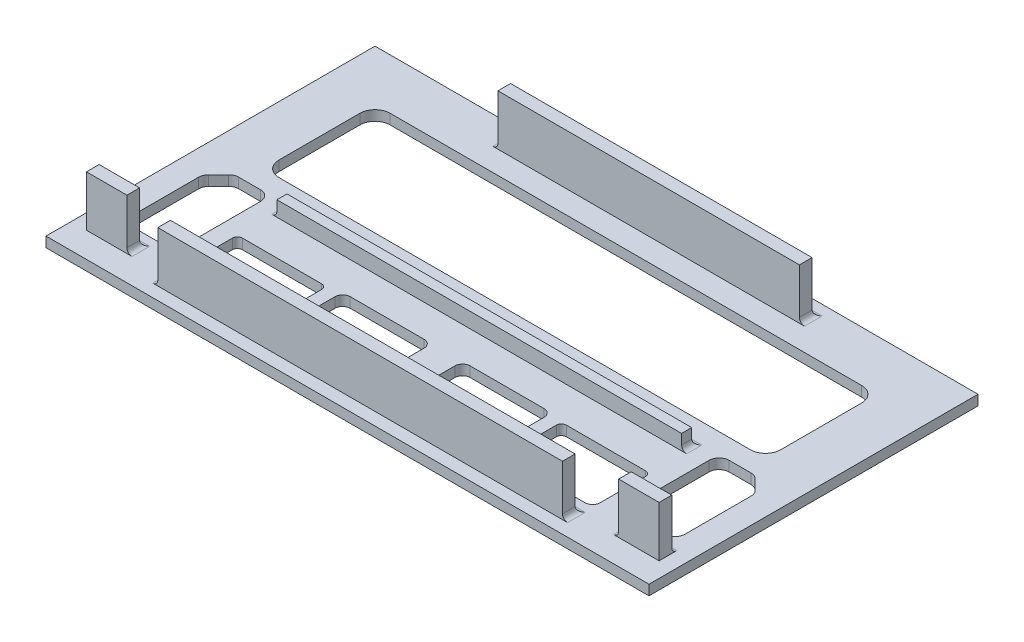
SolidWorks part; units mm, degrees
ref_plane "Front Plane" through (0, 0, 0) normal (0, 0, 1) x (1, 0, 0)
ref_plane "Top Plane" through (0, 0, 0) normal (0, 1, 0) x (1, 0, 0)
ref_plane "Right Plane" through (0, 0, 0) normal (1, 0, 0) x (0, 0, -1)
sketch "Sketch1" plane through (0, 0, 0) normal (0, 1, 0) x (1, 0, 0)
  line L1 (-59.6, -32.52) -> (59.6, -32.52)
  line L2 (-59.6, -32.52) -> (-59.6, 32.52)
  line L3 (-59.6, 32.52) -> (59.6, 32.52)
  line L4 (59.6, -32.52) -> (59.6, 32.52)
  line L5 (-59.6, -32.52) -> (59.6, 32.52) construction
  line L6 (-59.6, 32.52) -> (59.6, -32.52) construction
  point P0 (0, 0)
  dimension "D1" = 119.2
  dimension "D2" = 65.04
extrude "Boss-Extrude1" add sketch "Sketch1" along normal blind 2
ref_plane "Plane1" through (0, 0, 0) normal (-1, 0, 0) x (0, 0, 1)
sketch "Sketch2" plane through (0, 2, 0) normal (0, 1, 0) x (1, 0, 0)
  line L0 (-29.8, 29.52) -> (29.8, 29.52)
  line L1 (59.6, 32.52) -> (-59.6, 32.52) construction
  line L2 (59.6, -32.52) -> (59.6, 32.52) construction
  line L3 (59.6, -27.02) -> (59.6, -29.52)
  line L4 (29.8, 27.02) -> (-29.8, 27.02)
  line L5 (40, -4.48) -> (-40, -4.48)
  line L7 (-29.8, 29.52) -> (-29.8, 27.02)
  line L8 (29.8, 29.52) -> (29.8, 27.02)
  line L9 (-40, -4.48) -> (-40, -6.48)
  line L10 (-40, -6.48) -> (40, -6.48)
  line L11 (40, -6.48) -> (40, -4.48)
  dimension "D1" = 3
  dimension "D2" = 2.5
  dimension "D3" = 39
  dimension "D4" = 29.8
  dimension "D5" = 2
  dimension "D9" = 80
extrude "Boss-Extrude2" add sketch "Sketch2" along normal blind 10 contours L10 L11 L5 L9 | L8 L0 L7 L4 region at (0, 2, -28.27) region at (0, 2, 5.48)
fillet "Fillet1" radius 1 6 edges at (-29.8, 2, -28.27) (29.8, 2, -28.27) (0, 2, -29.52) (-40, 2, 5.48) (40, 2, 5.48) (0, 2, 4.48)
sketch "Sketch3" plane through (0, 12, 0) normal (0, 1, 0) x (1, 0, 0)
  line L0 (-40, -6.48) -> (40, -6.48) construction
  line L1 (40, -6.48) -> (40, -4.48) construction
  line L2 (40, -4.48) -> (-40, -4.48) construction
  line L3 (-40, -4.48) -> (-40, -6.48) construction
  line L4 (40, -8.48) -> (-40, -8.48) construction
  line L5 (-40, -8.48) -> (-40, -10.48) construction
  line L6 (-40, -10.48) -> (40, -10.48) construction
  line L7 (40, -10.48) -> (40, -8.48) construction
  line L8 (-40, -6.48) -> (40, -6.48)
  line L9 (40, -6.48) -> (40, -4.48)
  line L10 (40, -4.48) -> (-40, -4.48)
  line L11 (-40, -4.48) -> (-40, -6.48)
  line L12 (40, -8.48) -> (-40, -8.48)
  line L13 (-40, -8.48) -> (-40, -10.48)
  line L14 (-40, -10.48) -> (40, -10.48)
  line L15 (40, -10.48) -> (40, -8.48)
extrude "Cut-Extrude1" cut sketch "Sketch3" against normal blind 7
sketch "Sketch4" plane through (0, 2, 0) normal (0, 1, 0) x (1, 0, 0)
  line L0 (40, -30.02) -> (-40, -30.02)
  line L1 (-40, -30.02) -> (-40, -27.52)
  line L2 (-40, -27.52) -> (40, -27.52)
  line L3 (40, -27.52) -> (40, -30.02)
  line L4 (-59.6, -32.52) -> (59.6, -32.52) construction
  line L5 (0, 1.1) -> (0, -1.1) construction
  line L6 (48.6, -27.52) -> (56.6, -27.52)
  line L7 (56.6, -27.52) -> (56.6, -25.02)
  line L8 (56.6, -25.02) -> (48.6, -25.02)
  line L9 (48.6, -25.02) -> (48.6, -27.52)
  line L15 (59.6, -32.52) -> (59.6, 32.52) construction
  point P6 (0, -27.52)
  point P15 (52.6, -27.52)
  dimension "D1" = 2.5
  dimension "D2" = 2.5
  dimension "D3" = 80
  dimension "D4" = 2.5
  dimension "D6" = 3
  dimension "D7" = 8
extrude "Boss-Extrude3" add sketch "Sketch4" along normal blind 10
fillet "Fillet2" radius 1 5 edges at (-40, 2, 28.77) (48.6, 2, 26.27) (52.6, 2, 25.02) (40, 2, 28.77) (0, 2, 27.52)
mirror "Mirror1" about plane through (0, 0, 0) normal (-1, 0, 0) of "Boss-Extrude3"
fillet "Fillet3" radius 1 2 edges at (-52.6, 2, 25.02) (-48.6, 2, 26.27)
sketch "Sketch5" plane through (0, 2, 0) normal (0, 1, 0) x (1, 0, 0)
  line L0 (46.6, 22.52) -> (6.3115, 22.52)
  line L1 (6.3115, 22.52) -> (-46.6, 22.52)
  line L2 (-49.6, 19.52) -> (-49.6, 3.52)
  line L3 (-46.6, 0.52) -> (46.6, 0.52)
  line L4 (49.6, 3.52) -> (49.6, 19.52)
  line L5 (59.6, 32.52) -> (-59.6, 32.52) construction
  line L6 (59.6, -32.52) -> (59.6, 32.52) construction
  line L7 (-59.6, 32.52) -> (-59.6, -32.52) construction
  arc A0 (-49.6, 3.52) -> (-46.6, 0.52) centre (-46.6, 3.52) ccw
  arc A1 (-46.6, 22.52) -> (-49.6, 19.52) centre (-46.6, 19.52) ccw
  arc A2 (46.6, 22.52) -> (49.6, 19.52) centre (46.6, 19.52) cw
  arc A3 (46.6, 0.52) -> (49.6, 3.52) centre (46.6, 3.52) ccw
  dimension "D5" = 3
  dimension "D1" = 10
  dimension "D2" = 10
  dimension "D3" = 10
  dimension "D4" = 22
extrude "Cut-Extrude2" cut sketch "Sketch5" against normal blind 10
sketch "Sketch6" plane through (0, 2, 0) normal (0, 1, 0) x (1, 0, 0)
  line L3 (54.0142, -5.9408) -> (52.0453, -3.9719)
  line L4 (50.6311, -3.3862) -> (46.3278, -3.3862)
  line L5 (54.6, -7.3551) -> (54.6, -20.3979)
  line L6 (52.6, -22.3979) -> (46.3278, -22.3979)
  line L7 (44.3278, -20.3979) -> (44.3278, -5.3862)
  line L10 (39.8278, -13.4493) -> (24.2108, -13.4493)
  line L16 (4.044, -24.8936) -> (19.6609, -24.8936)
  line L17 (40.8278, -14.4493) -> (40.8278, -23.3936)
  line L18 (39.3278, -24.8936) -> (24.7108, -24.8936)
  line L19 (23.2108, -23.3936) -> (23.2108, -14.4493)
  line L21 (20.6609, -23.8936) -> (20.6609, -14.3214)
  line L22 (19.1609, -12.8214) -> (4.544, -12.8214)
  line L23 (3.044, -14.3214) -> (3.044, -23.8936)
  line L25 (59.6, -32.52) -> (59.6, 32.52) construction
  line L26 (0, -47.4967) -> (0, 52.968) construction
  line L29 (-4.044, -24.8936) -> (-19.6609, -24.8936)
  line L31 (-3.044, -14.3214) -> (-3.044, -23.8936)
  line L33 (-19.1609, -12.8214) -> (-4.544, -12.8214)
  line L34 (-20.6609, -23.8936) -> (-20.6609, -14.3214)
  line L37 (-39.3278, -24.8936) -> (-24.7108, -24.8936)
  line L39 (-39.8278, -13.4493) -> (-24.2108, -13.4493)
  line L40 (-23.2108, -14.4493) -> (-23.2108, -23.3936)
  line L42 (-40.8278, -23.3936) -> (-40.8278, -14.4493)
  line L43 (-44.3278, -5.3862) -> (-44.3278, -20.3979)
  line L44 (-50.6311, -3.3862) -> (-46.3278, -3.3862)
  line L45 (-54.0142, -5.9408) -> (-52.0453, -3.9719)
  line L46 (-54.6, -20.3979) -> (-54.6, -7.3551)
  line L51 (-52.6, -22.3979) -> (-46.3278, -22.3979)
  arc A1 (44.3278, -5.3862) -> (46.3278, -3.3862) centre (46.3278, -5.3862) cw
  arc A2 (52.0453, -3.9719) -> (50.6311, -3.3862) centre (50.6311, -5.3862) ccw
  arc A3 (54.6, -7.3551) -> (54.0142, -5.9408) centre (52.6, -7.3551) ccw
  arc A5 (46.3278, -22.3979) -> (44.3278, -20.3979) centre (46.3278, -20.3979) cw
  arc A8 (54.6, -20.3979) -> (52.6, -22.3979) centre (52.6, -20.3979) cw
  arc A10 (4.544, -12.8214) -> (3.044, -14.3214) centre (4.544, -14.3214) ccw
  arc A11 (20.6609, -14.3214) -> (19.1609, -12.8214) centre (19.1609, -14.3214) ccw
  arc A15 (24.7108, -24.8936) -> (23.2108, -23.3936) centre (24.7108, -23.3936) cw
  arc A16 (40.8278, -23.3936) -> (39.3278, -24.8936) centre (39.3278, -23.3936) cw
  arc A18 (3.044, -23.8936) -> (4.044, -24.8936) centre (4.044, -23.8936) ccw
  arc A19 (20.6609, -23.8936) -> (19.6609, -24.8936) centre (19.6609, -23.8936) cw
  arc A21 (40.8278, -14.4493) -> (39.8278, -13.4493) centre (39.8278, -14.4493) ccw
  arc A23 (24.2108, -13.4493) -> (23.2108, -14.4493) centre (24.2108, -14.4493) ccw
  arc A26 (-3.044, -23.8936) -> (-4.044, -24.8936) centre (-4.044, -23.8936) cw
  arc A27 (-20.6609, -23.8936) -> (-19.6609, -24.8936) centre (-19.6609, -23.8936) ccw
  arc A29 (-4.544, -12.8214) -> (-3.044, -14.3214) centre (-4.544, -14.3214) cw
  arc A31 (-20.6609, -14.3214) -> (-19.1609, -12.8214) centre (-19.1609, -14.3214) cw
  arc A35 (-40.8278, -23.3936) -> (-39.3278, -24.8936) centre (-39.3278, -23.3936) ccw
  arc A36 (-24.7108, -24.8936) -> (-23.2108, -23.3936) centre (-24.7108, -23.3936) ccw
  arc A37 (-24.2108, -13.4493) -> (-23.2108, -14.4493) centre (-24.2108, -14.4493) cw
  arc A40 (-40.8278, -14.4493) -> (-39.8278, -13.4493) centre (-39.8278, -14.4493) cw
  arc A41 (-44.3278, -5.3862) -> (-46.3278, -3.3862) centre (-46.3278, -5.3862) ccw
  arc A43 (-52.0453, -3.9719) -> (-50.6311, -3.3862) centre (-50.6311, -5.3862) cw
  arc A44 (-54.6, -7.3551) -> (-54.0142, -5.9408) centre (-52.6, -7.3551) cw
  arc A46 (-46.3278, -22.3979) -> (-44.3278, -20.3979) centre (-46.3278, -20.3979) ccw
  arc A49 (-54.6, -20.3979) -> (-52.6, -22.3979) centre (-52.6, -20.3979) ccw
  point P66 (3.044, -22.0111)
  point P71 (20.6609, -24.8936)
  point P74 (20.6609, -22.0111)
  dimension "D1" = 5
  dimension "D8" = 3.5
extrude "Cut-Extrude3" cut sketch "Sketch6" against normal blind 10
